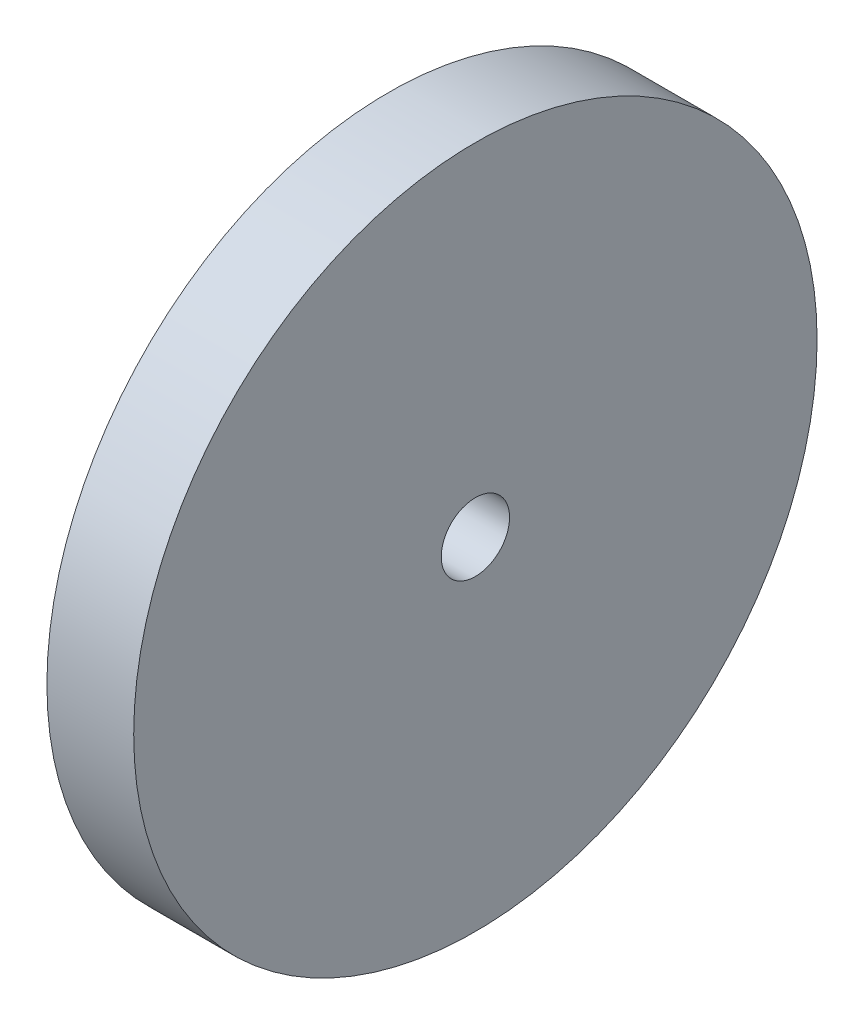
SolidWorks part; units mm, degrees
ref_plane "Front Plane" through (0, 0, 0) normal (0, 0, 1) x (1, 0, 0)
ref_plane "Top Plane" through (0, 0, 0) normal (0, 1, 0) x (1, 0, 0)
ref_plane "Right Plane" through (0, 0, 0) normal (1, 0, 0) x (0, 0, -1)
sketch "Sketch1" plane through (0, 0, 0) normal (1, 0, 0) x (0, 0, -1)
  circle A0 centre (0, 0) radius 50
  circle A1 centre (0, 0) radius 5
  dimension "D1" = 100
  dimension "D2" = 10
extrude "Boss-Extrude1" add sketch "Sketch1" along normal blind 12.7
